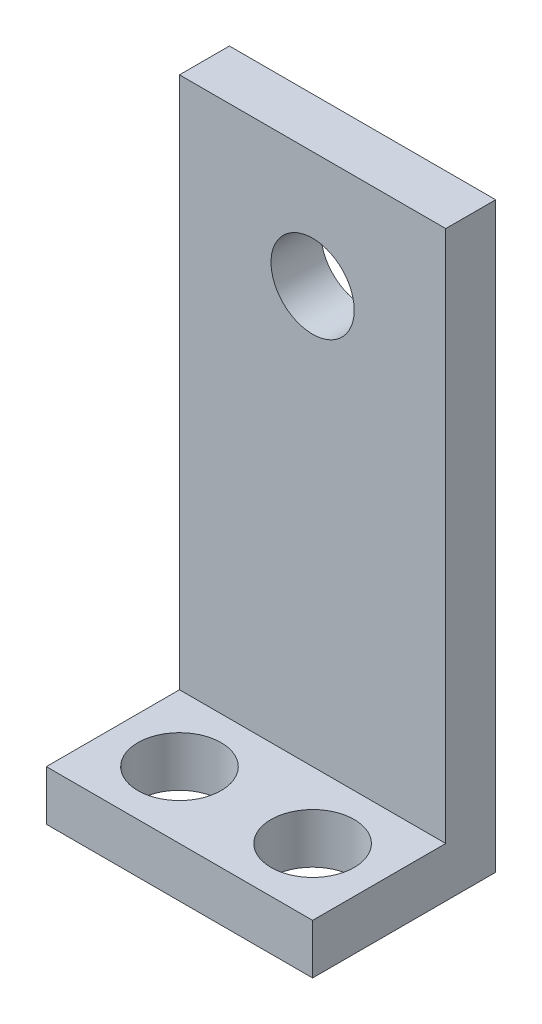
SolidWorks part; units mm, degrees
ref_plane "Front Plane" through (0, 0, 0) normal (0, 0, 1) x (1, 0, 0)
ref_plane "Top Plane" through (0, 0, 0) normal (0, 1, 0) x (1, 0, 0)
ref_plane "Right Plane" through (0, 0, 0) normal (1, 0, 0) x (0, 0, -1)
sketch "Sketch1" plane through (0, 0, 0) normal (0, 1, 0) x (1, 0, 0)
  line L0 (-8, 2.5) -> (8, 2.5)
  line L1 (-8, 5.5) -> (8, 5.5)
  line L2 (-8, 5.5) -> (-8, -5.5)
  line L3 (-8, -5.5) -> (8, -5.5)
  line L4 (8, 5.5) -> (8, -5.5)
  line L5 (-8, 5.5) -> (8, -5.5) construction
  line L6 (-8, -5.5) -> (8, 5.5) construction
  circle A0 centre (4, -1.5) radius 2.5
  circle A1 centre (-4, -1.5) radius 2.5
  point P0 (0, 0)
  dimension "D4" = 4
  dimension "D1" = 3
  dimension "D2" = 8
  dimension "D3" = 16
  dimension "D5" = 4
  dimension "D6" = 4
  dimension "D7" = 8
extrude "Boss-Extrude1" add sketch "Sketch1" along normal blind 35 contours L4 L1 L2 L0 region at (0, 0, -4)
extrude "Boss-Extrude2" add sketch "Sketch1<3>" along normal blind 3 contours L4 L0 L2 L3 region at (0, 0, 1.5)
sketch "Sketch1<3>" plane through (0, 0, 0) normal (0, 1, 0) x (1, 0, 0) same geometry as "Sketch1"
sketch "Sketch2" plane through (0, 0, -2.5) normal (0, 0, 1) x (1, 0, 0)
  circle A0 centre (0, 28) radius 2.5
  dimension "D2" = 5
extrude "Cut-Extrude1" cut sketch "Sketch2" against normal blind 8
